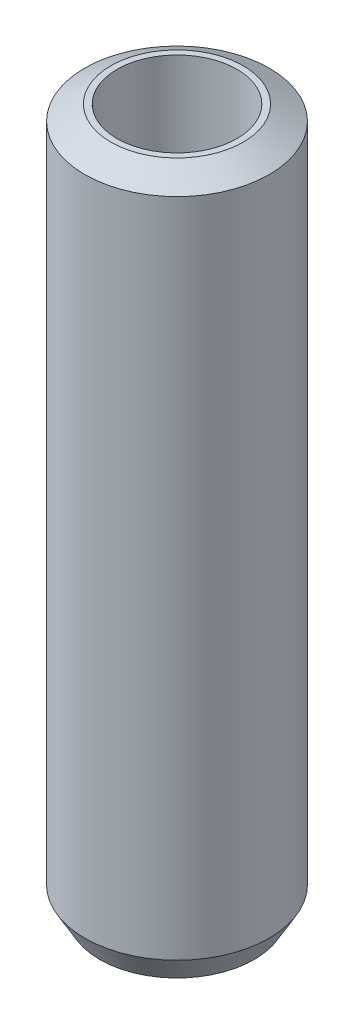
SolidWorks part; units mm, degrees
ref_plane "Front Plane" through (0, 0, 0) normal (0, 0, 1) x (1, 0, 0)
ref_plane "Top Plane" through (0, 0, 0) normal (0, 1, 0) x (1, 0, 0)
ref_plane "Right Plane" through (0, 0, 0) normal (1, 0, 0) x (0, 0, -1)
sketch "Sketch1" plane through (0, 0, 0) normal (0, 1, 0) x (1, 0, 0)
  circle A0 centre (0, 0) radius 32.5
  dimension "SHAFT_OD" = 65
extrude "Boss-Extrude1" add sketch "Sketch1" along normal blind 247.4599
sketch "Sketch2" plane through (0, 0, 0) normal (0, 1, 0) x (1, 0, 0)
  circle A0 centre (0, 0) radius 21.1432
  dimension "BORE_D" = 42.2863
extrude "Cut-Extrude1" cut sketch "Sketch2" along normal through all
chamfer "Chamfer1" distance 5.2981 angle 60 2 edges at (0, 247.4599, 32.5) (0, 0, 32.5) first distance on face at (0, 247.4599, 32.5) first distance on face at (0, 0, 21.1432)
